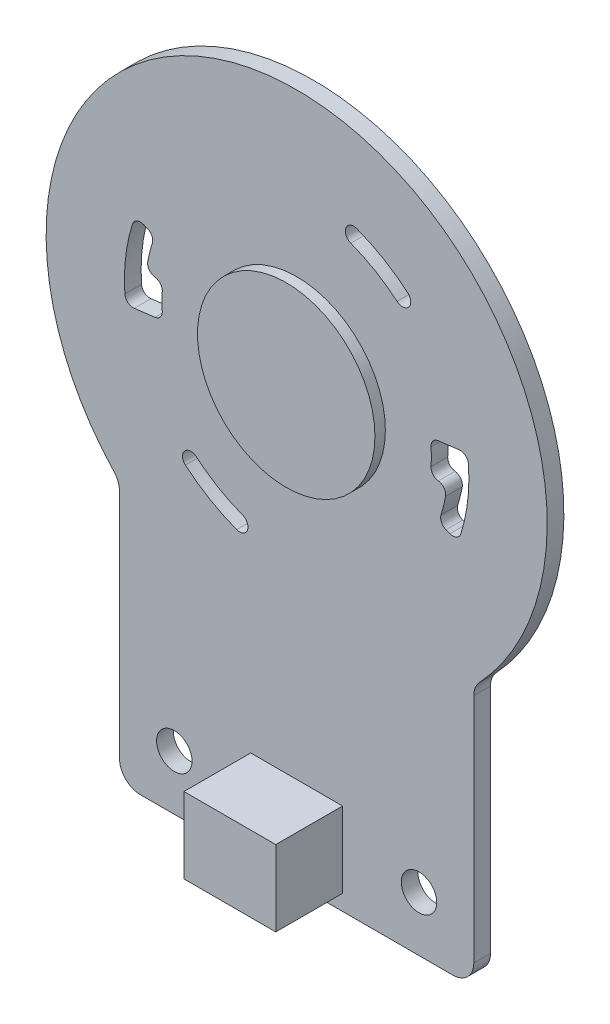
SolidWorks part; units mm, degrees
ref_plane "Front Plane" through (0, 0, 0) normal (0, 0, 1) x (1, 0, 0)
ref_plane "Top Plane" through (0, 0, 0) normal (0, 1, 0) x (1, 0, 0)
ref_plane "Right Plane" through (0, 0, 0) normal (1, 0, 0) x (0, 0, -1)
sketch "Sketch1" plane through (0, 0, 0) normal (0, 0, 1) x (1, 0, 0)
  line L0 (0, -38.4823) -> (0, 38.4823) construction
  line L1 (-18.1008, 0) -> (18.1008, 0) construction
  line L2 (15.4551, -5.7784) -> (0, 0) construction
  line L3 (16.377, 2.0108) -> (0, 0) construction
  line L4 (16.377, 2.0108) -> (12.8038, 1.5721)
  line L5 (12.8038, -1.5721) -> (0, 0) construction
  line L6 (12.8038, -1.5721) -> (14.3919, -1.7671)
  line L7 (15.4551, -5.7784) -> (13.5817, -5.078)
  line L8 (-16.9706, -16.9706) -> (0, 0) construction
  line L9 (16.9706, -16.9706) -> (0, 0) construction
  line L10 (-16.9706, -16.9706) -> (-16.9706, -39.9706)
  line L11 (16.9706, -16.9706) -> (16.9706, -39.9706)
  line L12 (-14.9706, -41.9706) -> (14.9706, -41.9706)
  line L16 (-16.377, -2.0108) -> (-12.8038, -1.5721)
  line L17 (-15.4551, 5.7784) -> (-13.5817, 5.078)
  line L18 (-12.8038, 1.5721) -> (-14.3919, 1.7671)
  line L19 (-9.6118, -11.254) -> (0, 0) construction
  line L20 (-5.1831, -13.8627) -> (0, 0) construction
  line L21 (5.4632, 14.6121) -> (0, 0) construction
  line L22 (10.1314, 11.8623) -> (0, 0) construction
  arc A0 (15.4551, -5.7784) -> (16.377, 2.0108) centre (0, 0) ccw
  arc A1 (12.8038, 1.5721) -> (12.8038, -1.5721) centre (0, 0) cw
  arc A2 (13.5817, -5.078) -> (14.3919, -1.7671) centre (0, 0) ccw
  arc A4 (16.9706, -16.9706) -> (-16.9706, -16.9706) centre (0, 0) ccw
  arc A5 (-16.9706, -39.9706) -> (-14.9706, -41.9706) centre (-14.9706, -39.9706) ccw
  arc A6 (14.9706, -41.9706) -> (16.9706, -39.9706) centre (14.9706, -39.9706) ccw
  arc A7 (-12.8038, 1.5721) -> (-12.8038, -1.5721) centre (0, 0) ccw
  arc A10 (-15.4551, 5.7784) -> (-16.377, -2.0108) centre (0, 0) ccw
  arc A11 (-13.5817, 5.078) -> (-14.3919, 1.7671) centre (0, 0) ccw
  arc A12 (-9.6118, -11.254) -> (-5.1831, -13.8627) centre (0, 0) ccw
  arc A13 (-10.6509, -12.4707) -> (-5.7434, -15.3614) centre (0, 0) ccw
  arc A14 (-9.6118, -11.254) -> (-10.6509, -12.4707) centre (-10.1314, -11.8623) ccw
  arc A15 (-5.7434, -15.3614) -> (-5.1831, -13.8627) centre (-5.4632, -14.6121) ccw
  arc A16 (5.7434, 15.3614) -> (5.1831, 13.8627) centre (5.4632, 14.6121) ccw
  arc A17 (9.6118, 11.254) -> (5.1831, 13.8627) centre (0, 0) ccw
  arc A18 (9.6118, 11.254) -> (10.6509, 12.4707) centre (10.1314, 11.8623) ccw
  arc A19 (10.6509, 12.4707) -> (5.7434, 15.3614) centre (0, 0) ccw
  point P7 (0, 0)
  point P10 (0, 0)
  point P43 (0, 0)
  dimension "D1" = 16.5
  dimension "D6" = 24
  dimension "D12" = 2
  dimension "D13" = 16.5
  dimension "D14" = 14.5
  dimension "D15" = 14.8
  dimension "D18" = 16.4
  dimension "D2" = 20.5
  dimension "D3" = 7
  dimension "D4" = 3.6
  dimension "D5" = 7
  dimension "D7" = 2
  dimension "D8" = 45
  dimension "D9" = 45
  dimension "D10" = 23
  dimension "D11" = 23
  dimension "D16" = 42.5
  dimension "D17" = 20
  dimension "D20" = 42.5
  dimension "D19" = 2
extrude "Outline" add sketch "Sketch1" along normal blind 1.6
fillet "Fillets" radius 0.8 12 edges at (16.377, 2.0108, 0.8) (12.8038, 1.5721, 0.8) (13.5817, -5.078, 0.8) (15.4551, -5.7784, 0.8) (14.3919, -1.7671, 0.8) (12.8038, -1.5721, 0.8) (-12.8038, -1.5721, 0.8) (-16.377, -2.0108, 0.8) (-15.4551, 5.7784, 0.8) (-13.5817, 5.078, 0.8) (-12.8038, 1.5721, 0.8) (-14.3919, 1.7671, 0.8)
fillet "Fillet2" radius 2 2 edges at (16.9706, -16.9706, 0.8) (-16.9706, -16.9706, 0.8)
sketch "Sketch2" plane through (0, 0, 1.6) normal (0, 0, 1) x (1, 0, 0)
  line L0 (-14.3115, 5.3508) -> (-14.6866, 5.4911) construction
  line L1 (-16.9706, -17.7797) -> (-16.9706, -39.9706) construction
  line L2 (-14.9706, -41.9706) -> (14.9706, -41.9706) construction
  line L3 (16.9706, -39.9706) -> (16.9706, -17.7797) construction
  line L4 (14.3115, -5.3508) -> (14.6866, -5.4911) construction
  line L5 (15.5627, 1.9109) -> (13.5747, 1.6668) construction
  line L6 (-15.5627, -1.9109) -> (-13.5747, -1.6668) construction
  line L7 (-16.9706, -17.7797) -> (-16.9706, -39.9706)
  line L8 (-14.9706, -41.9706) -> (14.9706, -41.9706)
  line L9 (16.9706, -39.9706) -> (16.9706, -17.7797)
  line L10 (14.3115, -5.3508) -> (14.6866, -5.4911)
  line L11 (15.5627, 1.9109) -> (13.5747, 1.6668)
  line L12 (-15.5627, -1.9109) -> (-13.5747, -1.6668)
  line L13 (-14.3115, 5.3508) -> (-14.6866, 5.4911)
  arc A0 (-14.6866, 5.4911) -> (-15.7295, 4.9834) centre (-14.9668, 4.7418) ccw construction
  arc A1 (-16.9706, -17.7797) -> (-17.5113, -16.412) centre (-18.9706, -17.7797) ccw construction
  arc A2 (-16.9706, -39.9706) -> (-14.9706, -41.9706) centre (-14.9706, -39.9706) ccw construction
  arc A3 (14.9706, -41.9706) -> (16.9706, -39.9706) centre (14.9706, -39.9706) ccw construction
  arc A4 (17.5113, -16.412) -> (16.9706, -17.7797) centre (18.9706, -17.7797) ccw construction
  arc A5 (17.5113, -16.412) -> (-17.5113, -16.412) centre (0, 0) ccw construction
  arc A6 (5.7434, 15.3614) -> (5.1831, 13.8627) centre (5.4632, 14.6121) ccw construction
  arc A7 (10.6509, 12.4707) -> (5.7434, 15.3614) centre (0, 0) ccw construction
  arc A8 (9.6118, 11.254) -> (5.1831, 13.8627) centre (0, 0) ccw construction
  arc A9 (9.6118, 11.254) -> (10.6509, 12.4707) centre (10.1314, 11.8623) ccw construction
  arc A10 (14.6866, -5.4911) -> (15.7295, -4.9834) centre (14.9668, -4.7418) ccw construction
  arc A11 (13.8287, -4.3609) -> (14.3115, -5.3508) centre (14.5916, -4.6015) ccw construction
  arc A12 (15.7295, -4.9834) -> (16.4582, 1.1737) centre (0, 0) ccw construction
  arc A13 (16.4582, 1.1737) -> (15.5627, 1.9109) centre (15.6602, 1.1168) ccw construction
  arc A14 (13.5747, 1.6668) -> (12.8738, 0.8218) centre (13.6722, 0.8727) ccw construction
  arc A15 (12.8738, -0.8218) -> (12.8738, 0.8218) centre (0, 0) ccw construction
  arc A16 (12.8738, -0.8218) -> (13.5747, -1.6668) centre (13.6722, -0.8727) ccw construction
  arc A17 (14.2642, -2.6045) -> (13.5747, -1.6668) centre (13.4772, -2.4608) ccw construction
  arc A18 (13.8287, -4.3609) -> (14.2642, -2.6045) centre (0, 0) ccw construction
  arc A19 (-9.6118, -11.254) -> (-10.6509, -12.4707) centre (-10.1314, -11.8623) ccw construction
  arc A20 (-9.6118, -11.254) -> (-5.1831, -13.8627) centre (0, 0) ccw construction
  arc A21 (-5.7434, -15.3614) -> (-5.1831, -13.8627) centre (-5.4632, -14.6121) ccw construction
  arc A22 (-10.6509, -12.4707) -> (-5.7434, -15.3614) centre (0, 0) ccw construction
  arc A23 (-14.2642, 2.6045) -> (-13.5747, 1.6668) centre (-13.4772, 2.4608) ccw construction
  arc A24 (-12.8738, 0.8218) -> (-13.5747, 1.6668) centre (-13.6722, 0.8727) ccw construction
  arc A25 (-12.8738, 0.8218) -> (-12.8738, -0.8218) centre (0, 0) ccw construction
  arc A26 (-13.5747, -1.6668) -> (-12.8738, -0.8218) centre (-13.6722, -0.8727) ccw construction
  arc A27 (-16.4582, -1.1737) -> (-15.5627, -1.9109) centre (-15.6602, -1.1168) ccw construction
  arc A28 (-15.7295, 4.9834) -> (-16.4582, -1.1737) centre (0, 0) ccw construction
  arc A29 (-13.8287, 4.3609) -> (-14.2642, 2.6045) centre (0, 0) ccw construction
  arc A30 (-13.8287, 4.3609) -> (-14.3115, 5.3508) centre (-14.5916, 4.6015) ccw construction
  arc A31 (-16.9706, -17.7797) -> (-17.5113, -16.412) centre (-18.9706, -17.7797) ccw
  arc A32 (-16.9706, -39.9706) -> (-14.9706, -41.9706) centre (-14.9706, -39.9706) ccw
  arc A33 (14.9706, -41.9706) -> (16.9706, -39.9706) centre (14.9706, -39.9706) ccw
  arc A34 (17.5113, -16.412) -> (16.9706, -17.7797) centre (18.9706, -17.7797) ccw
  arc A35 (17.5113, -16.412) -> (-17.5113, -16.412) centre (0, 0) ccw
  arc A36 (5.7434, 15.3614) -> (5.1831, 13.8627) centre (5.4632, 14.6121) ccw
  arc A37 (10.6509, 12.4707) -> (5.7434, 15.3614) centre (0, 0) ccw
  arc A38 (9.6118, 11.254) -> (5.1831, 13.8627) centre (0, 0) ccw
  arc A39 (9.6118, 11.254) -> (10.6509, 12.4707) centre (10.1314, 11.8623) ccw
  arc A40 (14.6866, -5.4911) -> (15.7295, -4.9834) centre (14.9668, -4.7418) ccw
  arc A41 (13.8287, -4.3609) -> (14.3115, -5.3508) centre (14.5916, -4.6015) ccw
  arc A42 (15.7295, -4.9834) -> (16.4582, 1.1737) centre (0, 0) ccw
  arc A43 (16.4582, 1.1737) -> (15.5627, 1.9109) centre (15.6602, 1.1168) ccw
  arc A44 (13.5747, 1.6668) -> (12.8738, 0.8218) centre (13.6722, 0.8727) ccw
  arc A45 (12.8738, -0.8218) -> (12.8738, 0.8218) centre (0, 0) ccw
  arc A46 (12.8738, -0.8218) -> (13.5747, -1.6668) centre (13.6722, -0.8727) ccw
  arc A47 (14.2642, -2.6045) -> (13.5747, -1.6668) centre (13.4772, -2.4608) ccw
  arc A48 (13.8287, -4.3609) -> (14.2642, -2.6045) centre (0, 0) ccw
  arc A49 (-9.6118, -11.254) -> (-10.6509, -12.4707) centre (-10.1314, -11.8623) ccw
  arc A50 (-9.6118, -11.254) -> (-5.1831, -13.8627) centre (0, 0) ccw
  arc A51 (-5.7434, -15.3614) -> (-5.1831, -13.8627) centre (-5.4632, -14.6121) ccw
  arc A52 (-10.6509, -12.4707) -> (-5.7434, -15.3614) centre (0, 0) ccw
  arc A53 (-14.2642, 2.6045) -> (-13.5747, 1.6668) centre (-13.4772, 2.4608) ccw
  arc A54 (-12.8738, 0.8218) -> (-13.5747, 1.6668) centre (-13.6722, 0.8727) ccw
  arc A55 (-12.8738, 0.8218) -> (-12.8738, -0.8218) centre (0, 0) ccw
  arc A56 (-13.5747, -1.6668) -> (-12.8738, -0.8218) centre (-13.6722, -0.8727) ccw
  arc A57 (-16.4582, -1.1737) -> (-15.5627, -1.9109) centre (-15.6602, -1.1168) ccw
  arc A58 (-15.7295, 4.9834) -> (-16.4582, -1.1737) centre (0, 0) ccw
  arc A59 (-13.8287, 4.3609) -> (-14.2642, 2.6045) centre (0, 0) ccw
  arc A60 (-13.8287, 4.3609) -> (-14.3115, 5.3508) centre (-14.5916, 4.6015) ccw
  arc A61 (-14.6866, 5.4911) -> (-15.7295, 4.9834) centre (-14.9668, 4.7418) ccw
sketch "Sketch3" plane through (0, 0, 1.6) normal (0, 0, 1) x (1, 0, 0)
  circle A0 centre (0, 0) radius 8.5
  dimension "D1" = 17
extrude "LED Ring Area" add sketch "Sketch3" along normal blind 1
sketch "Sketch4" plane through (0, 0, 1.6) normal (0, 0, 1) x (1, 0, 0)
  line L0 (-16.9706, -17.7797) -> (-16.9706, -39.9706) construction
  line L1 (16.9706, -39.9706) -> (16.9706, -17.7797) construction
  line L2 (-14.9706, -41.9706) -> (14.9706, -41.9706) construction
  circle A0 centre (-11.7206, -36.7206) radius 1.7
  circle A1 centre (11.7206, -36.7206) radius 1.7
  dimension "D1" = 3.4
  dimension "D2" = 5.25
  dimension "D3" = 5.25
  dimension "D4" = 5.25
extrude "Mounting Holes" cut sketch "Sketch4" against normal through all
sketch "Sketch5" plane through (0, 0, 1.6) normal (0, 0, 1) x (1, 0, 0)
  line L0 (0, 0) -> (0, -41.9706) construction
  line L1 (-4.4, -33.2206) -> (4.4, -33.2206)
  line L2 (-4.4, -33.2206) -> (-4.4, -40.4706)
  line L3 (-4.4, -40.4706) -> (4.4, -40.4706)
  line L4 (4.4, -33.2206) -> (4.4, -40.4706)
  line L5 (-14.9706, -41.9706) -> (14.9706, -41.9706) construction
  point P9 (0, -40.4706)
  dimension "D1" = 7.25
  dimension "D2" = 8.8
  dimension "D3" = 1.5
extrude "Connector Area" add sketch "Sketch5" along normal blind 6.4
